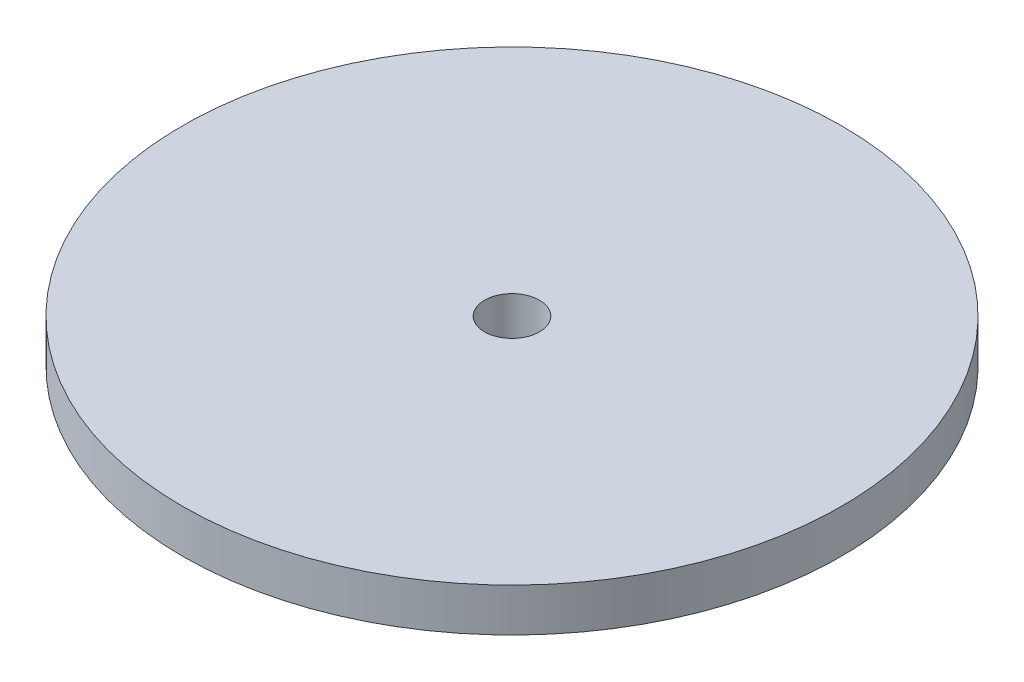
SolidWorks part; units mm, degrees
material "6061 Alloy"
ref_plane "Front Plane" through (0, 0, 0) normal (0, 0, 1) x (1, 0, 0)
ref_plane "Top Plane" through (0, 0, 0) normal (0, 1, 0) x (1, 0, 0)
ref_plane "Right Plane" through (0, 0, 0) normal (1, 0, 0) x (0, 0, -1)
sketch "Sketch2" plane through (0, 0, 0) normal (0, 1, 0) x (1, 0, 0)
  circle A0 centre (0, 0) radius 76.1746
  dimension "D1" = 152.3492
extrude "Boss-Extrude1" add sketch "Sketch2" along normal blind 10
sketch "Sketch3" plane through (0, 10, 0) normal (0, 1, 0) x (1, 0, 0)
  circle A0 centre (0, 0) radius 6.35
  dimension "D1" = 12.7
extrude "Cut-Extrude1" cut sketch "Sketch3" against normal through all both and the other way through all
